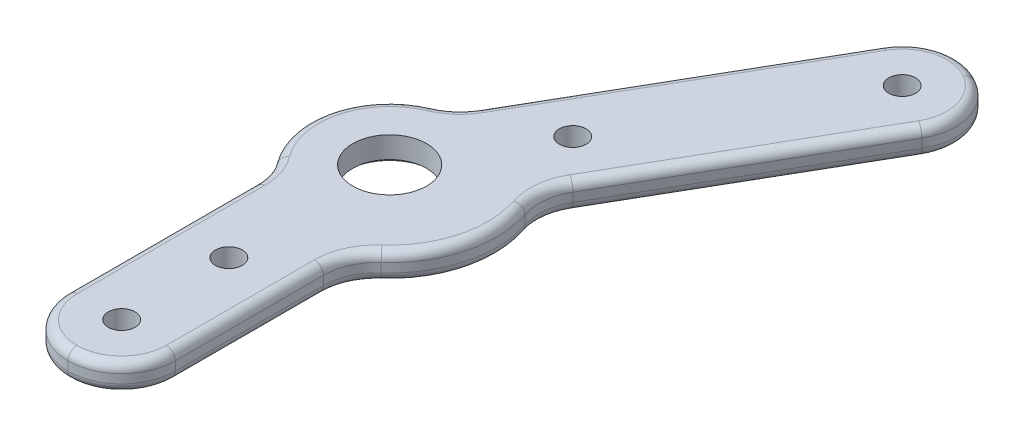
SolidWorks part; units mm, degrees
material "6061 Alloy"
ref_plane "Front Plane" through (0, 0, 0) normal (0, 0, 1) x (1, 0, 0)
ref_plane "Top Plane" through (0, 0, 0) normal (0, 1, 0) x (1, 0, 0)
ref_plane "Right Plane" through (0, 0, 0) normal (1, 0, 0) x (0, 0, -1)
sketch "Sketch1" plane through (0, 0, 0) normal (0, 1, 0) x (1, 0, 0)
  line L0 (0, 44.45) -> (0, -44.45) construction
  line L1 (-12.7, -44.45) -> (12.7, -44.45)
  line L2 (-12.7, -44.45) -> (-12.7, 31.75)
  line L3 (-12.7, 44.45) -> (12.7, 44.45) construction
  line L4 (12.7, -44.45) -> (12.7, 31.75)
  line L5 (-12.7, -44.45) -> (12.7, 44.45) construction
  line L6 (-12.7, 44.45) -> (12.7, -44.45) construction
  line L7 (0, 31.75) -> (50.8, 119.7382) construction
  line L8 (10.9985, 25.4) -> (61.7985, 113.3882)
  line L9 (61.7985, 113.3882) -> (39.8015, 126.0882)
  line L10 (39.8015, 126.0882) -> (-10.9985, 38.1)
  line L11 (-10.9985, 38.1) -> (10.9985, 25.4) construction
  line L12 (12.7, 44.45) -> (12.7, 31.75) construction
  line L13 (61.7985, 113.3882) -> (61.7985, -44.45) construction
  line L14 (61.7985, -44.45) -> (12.7, -44.45) construction
  line L15 (12.7, 44.45) -> (12.7, 79.147) construction
  circle A0 centre (0, 31.75) radius 12.7 construction
  circle A1 centre (0, -31.75) radius 3.175
  circle A2 centre (0, -6.35) radius 3.175
  circle A3 centre (0, 31.75) radius 8.7312
  circle A4 centre (44.45, 108.7397) radius 3.175
  circle A5 centre (15.875, 59.2463) radius 3.175
  circle A6 centre (0, 31.75) radius 19.05
  arc A7 (21.997, 44.45) -> (12.7, 9.753) centre (0, 31.75) cw
  point P0 (0, 0)
  point P16 (50.8, 119.7382)
  point P21 (0, 31.75)
  dimension "D4" = 12.7
  dimension "D1" = 6.35
  dimension "D7" = 88.9
  dimension "D8" = 12.7
  dimension "D9" = 17.4625
  dimension "D10" = 6.35
  dimension "D11" = 6.35
  dimension "D2" = 25.4
  dimension "D3" = 30
  dimension "D5" = 25.4
  dimension "D6" = 38.1
extrude "Boss-Extrude1" add sketch "Sketch1" along normal blind 6.35 contours A0 L2 L1 L4 L8 A2 A1 | A0 L4 L8 L9 L10 A4 | A0 L8 L4 | L4 A6 L8 | A7 L8 A6 L4 region at (0, 0, 14.9202) region at (-17.8869, 0, -36.5428) region at (19.9726, 0, -26.3983) region at (29.7636, 0, -83.3021) region at (15.7679, 0, -27.525)
fillet "Fillet2" radius 12.7 8 edges at (39.8015, 3.175, -126.0882) (61.7985, 3.175, -113.3882) (-12.7, 3.175, 44.45) (12.7, 3.175, 44.45) (-3.899, 3.175, -50.3967) (-12.7, 3.175, -17.551) (12.7, 3.175, -9.753) (21.997, 3.175, -44.45)
fillet "Fillet3" radius 2.1167 28 edges at (12.7, 0, 14.199) (8.9803, 0, 40.7303) (-8.9803, 0, 40.7303) (-12.7, 0, 9.525) (15.989, 0, -84.8437) (41.163, 0, -121.0069) (56.7173, 0, -112.0267) (12.7, 6.35, 14.199) (8.9803, 6.35, 40.7303) (-8.9803, 6.35, 40.7303) (-12.7, 6.35, 9.525) (15.989, 6.35, -84.8437) (41.163, 6.35, -121.0069) (56.7173, 6.35, -112.0267) (40.323, 0, -76.1916) (40.323, 6.35, -76.1916) (-18.4009, 0, -36.6805) (-13.3517, 0, -16.7161) (-4.046, 0, -51.4456) (-18.4009, 6.35, -36.6805) (-13.3517, 6.35, -16.7161) (-4.046, 6.35, -51.4456) (23.5635, 0, -44.95) (24.5345, 0, -25.176) (13.8065, 0, -8.5367) (23.5635, 6.35, -44.95) (24.5345, 6.35, -25.176) (13.8065, 6.35, -8.5367)
sketch "Sketch3" plane through (0, 0, 0) normal (0, -1, 0) x (1, 0, 0)
  circle A0 centre (0, -31.75) radius 10.2489
  dimension "D1" = 20.4978
extrude "Cut-Extrude1" cut sketch "Sketch3" against normal blind 1.27
